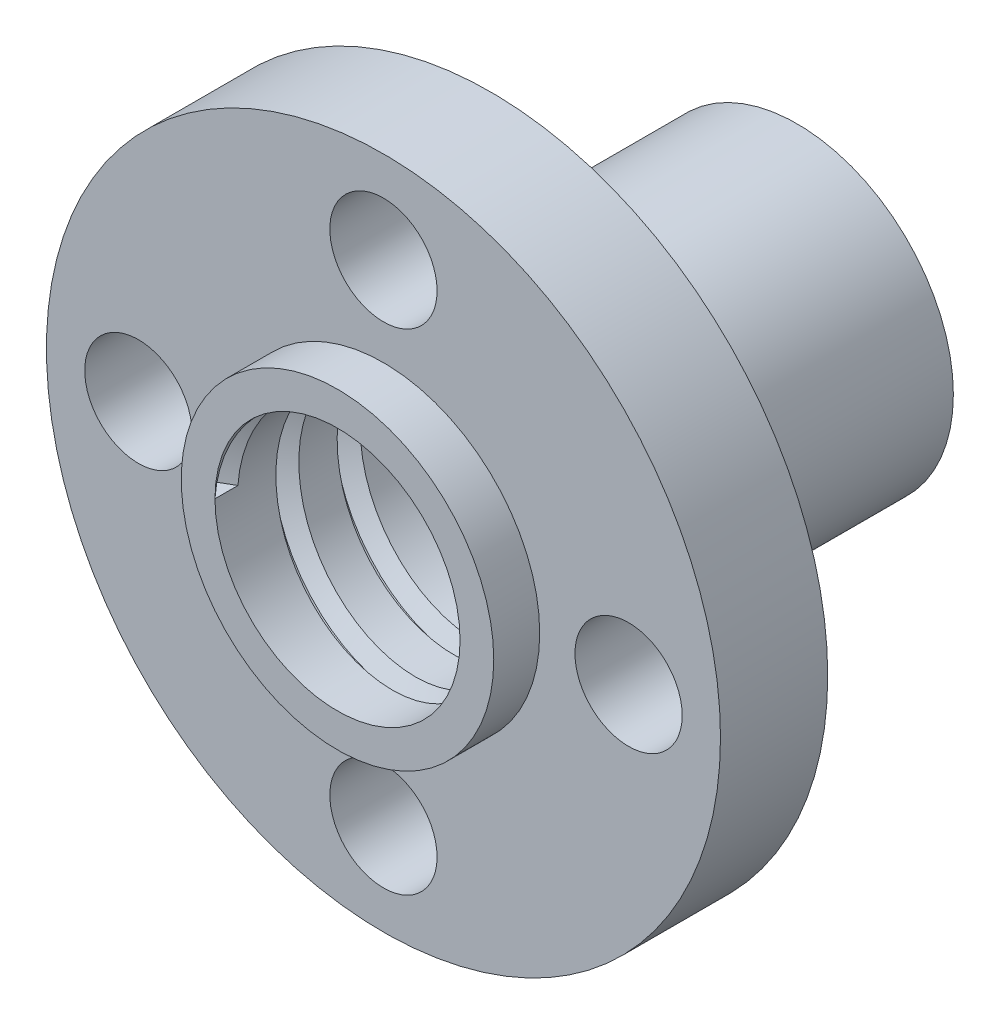
SolidWorks part; units mm, degrees
ref_plane "Plano frontal" through (0, 0, 0) normal (0, 0, 1) x (1, 0, 0)
ref_plane "Plano superior" through (0, 0, 0) normal (0, 1, 0) x (1, 0, 0)
ref_plane "Plano direito" through (0, 0, 0) normal (1, 0, 0) x (0, 0, -1)
sketch "Esboço1" plane through (0, 0, 0) normal (0, 0, 1) x (1, 0, 0)
  circle A0 centre (0, 0) radius 11
  dimension "D1" = 22
extrude "Ressalto-extrusão1" add sketch "Esboço1" along normal blind 3.5
sketch "Esboço2" plane through (0, 0, 3.5) normal (0, 0, 1) x (1, 0, 0)
  line L0 (0, -12.2209) -> (0, 12.4343) construction
  line L1 (-15.6827, 0) -> (15.0579, 0) construction
  circle A0 centre (0, 0) radius 8 construction
  circle A1 centre (0, 8) radius 1.75
  circle A2 centre (8, 0) radius 1.75
  circle A3 centre (0, -8) radius 1.75
  circle A4 centre (-8, 0) radius 1.75
  dimension "D1" = 3.5
  dimension "D2" = 4
extrude "Corte-extrusão1" cut sketch "Esboço2" against normal through all both and the other way through all
sketch "Esboço3" plane through (0, 0, 3.5) normal (0, 0, 1) x (1, 0, 0)
  circle A0 centre (0, 0) radius 5.1
  dimension "D1" = 10.2
extrude "Ressalto-extrusão2" add sketch "Esboço3" along normal blind 1.5
sketch "Esboço4" plane through (0, 0, 0) normal (0, 0, -1) x (-1, 0, 0)
  circle A0 centre (0, 0) radius 5.1
  dimension "D1" = 10.2
extrude "Ressalto-extrusão3" add sketch "Esboço4" along normal blind 10
sketch "Esboço5" plane through (0, 0, -10) normal (0, 0, -1) x (-1, 0, 0)
  circle A0 centre (0, 0) radius 4
  dimension "D1" = 8
extrude "Corte-extrusão2" cut sketch "Esboço5" against normal through all
thread "Rosca1" pitch 1 method cut profile "Perfil da rosca1" start angle 0, offset 0, length 0, pitch 2, diameter 8
ref_plane "Plano1" through (-4, 0, 5) normal (0, -1, 0) x (-1, 0, 0)
sketch "Perfil da rosca1" plane through (-4, 0, 5) normal (0, -1, 0) x (-1, 0, 0)
  line L0 (0, 0) -> (0, 1) construction
  line L1 (0, 0) -> (0.5413, 0.3125)
  line L2 (0.5413, 0.3125) -> (0.5413, 0.4375)
  line L3 (0.5413, 0.4375) -> (0, 0.75)
  line L4 (0.5413, 0.375) -> (0, 0.375) construction
  line L11 (0, 0) -> (0, 0.75)
  point P2 (0, 0)
  dimension "Pitch" = 1
  dimension "Profile_Angle" = 60
  dimension "Profile_Land" = 0.125
  dimension "Profile_Height" = 0.5413
